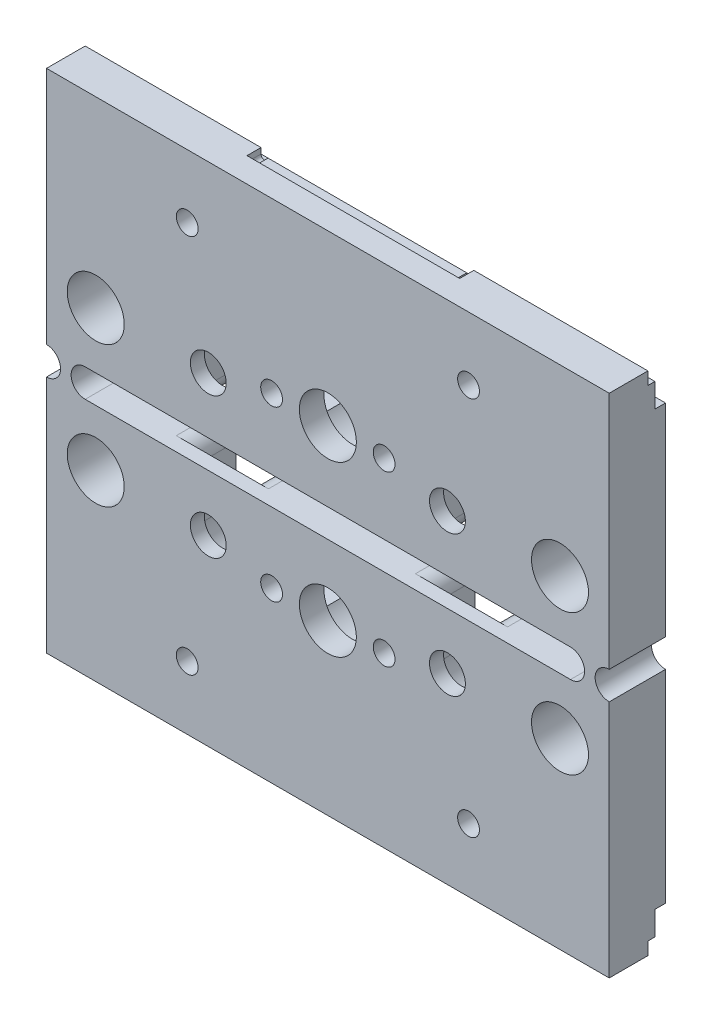
SolidWorks part; units mm, degrees
ref_plane "前视基准面" through (0, 0, 0) normal (0, 0, 1) x (1, 0, 0)
ref_plane "上视基准面" through (0, 0, 0) normal (0, 1, 0) x (1, 0, 0)
ref_plane "右视基准面" through (0, 0, 0) normal (1, 0, 0) x (0, 0, -1)
sketch "前视图草图" plane through (0, 0, 0) normal (0, 0, 1) x (1, 0, 0)
  line L0 (0, 0) -> (8.5179, 0) construction
  line L1 (0, 0) -> (0, 5.4227) construction
sketch "草图2" plane through (0, 0, 0) normal (0, 0, 1) x (1, 0, 0)
  line L0 (0, 0) -> (80, 0)
  line L1 (-200000, 0) -> (200008.5179, 0) construction
  line L2 (80, 0) -> (80, 34)
  line L3 (80, 34) -> (0, 34)
  line L4 (0, -200000) -> (0, 200005.4227) construction
  line L5 (0, 34) -> (0, 0)
  circle A0 centre (7, 8) radius 4.05
  circle A1 centre (40, 10) radius 4.05
  circle A2 centre (73, 8) radius 4.05
  dimension "D3" = 8
  dimension "D5" = 10
  dimension "D9" = 8.1
  dimension "D10" = 8.1
  dimension "D11" = 8.1
  dimension "D1" = 34
  dimension "D2" = 80
  dimension "D4" = 7
  dimension "D6" = 7
  dimension "D7" = 8
  dimension "D8" = 40
extrude "凸台-拉伸1" add sketch "草图2" along normal blind 8
sketch "草图3" plane through (0, 0, 8) normal (0, 0, 1) x (1, 0, 0)
  line L0 (16.088, 8) -> (31.4805, 8) construction
  line L1 (7, 8) -> (7, 16.8386) construction
  line L2 (73, 8) -> (73, 16.5917) construction
  line L4 (-200000, 0) -> (200008.5179, 0) construction
  circle A2 centre (23, 8) radius 2.55
  circle A3 centre (57, 8) radius 2.55
  dimension "D4" = 5.1
  dimension "D5" = 5.1
  dimension "D1" = 8
  dimension "D2" = 16
  dimension "D3" = 16
extrude "切除-拉伸1" cut sketch "草图3" against normal through all
sketch "草图4" plane through (80, 0, 0) normal (1, 0, 0) x (0, 0, -1)
  line L1 (0, -200000) -> (0, 200005.4227) construction
  line L2 (-1.5, 32.2) -> (-2.5, 32.2)
  line L3 (-2.5, 32.2) -> (-2.5, 34)
  line L4 (-8, 34) -> (0, 34) construction
  line L5 (-2.5, 34) -> (0, 34)
  line L6 (-1.5, 32.2) -> (-1.5, 28.8)
  line L7 (-1.5, 28.8) -> (0, 28.8)
  line L8 (0, 28.8) -> (0, 34)
  dimension "D1" = 3.4
  dimension "D2" = 2.5
  dimension "D3" = 1.5
  dimension "D4" = 1.8
extrude "切除-拉伸2" cut sketch "草图4" against normal through all
sketch "草图5" plane through (0, 0, 8) normal (0, 0, 1) x (1, 0, 0)
  line L0 (40, 10) -> (56.5376, 10) construction
  circle A0 centre (40, 10) radius 8 construction
  circle A1 centre (48, 10) radius 1.55
  circle A2 centre (32, 10) radius 1.55
  dimension "D1" = 3.1
  dimension "D2" = 3.1
  dimension "D3" = 16
extrude "切除-拉伸3" cut sketch "草图5" against normal through all
sketch "草图7" plane through (0, 0, 0) normal (0, 0, -1) x (-1, 0, 0)
  line L0 (-40, 12) -> (-40, -8.3696) construction
  line L1 (-23, 10) -> (-23, -2.3368) construction
  line L2 (200000, 0) -> (-200008.5179, 0) construction
  line L6 (-27.05, 10) -> (-27.05, 2.5)
  line L7 (-29.55, 0) -> (-16.45, 0)
  line L8 (-18.95, 2.5) -> (-18.95, 10)
  line L9 (-23, 8) -> (-23, 15.9045) construction
  line L13 (0, -200000) -> (0, 200005.4227) construction
  line L14 (-57, 8) -> (-57, 15.9045) construction
  line L15 (-57, 10) -> (-57, -2.3368) construction
  line L16 (-61.05, 2.5) -> (-61.05, 10)
  line L17 (-50.45, 0) -> (-63.55, 0)
  line L18 (-52.95, 10) -> (-52.95, 2.5)
  arc A1 (-18.95, 10) -> (-27.05, 10) centre (-23, 10) ccw
  arc A4 (-29.55, 0) -> (-27.05, 2.5) centre (-29.55, 2.5) ccw
  arc A5 (-18.95, 2.5) -> (-16.45, 0) centre (-16.45, 2.5) ccw
  arc A7 (-61.05, 2.5) -> (-63.55, 0) centre (-63.55, 2.5) cw
  arc A8 (-50.45, 0) -> (-52.95, 2.5) centre (-50.45, 2.5) cw
  arc A9 (-61.05, 10) -> (-52.95, 10) centre (-57, 10) cw
  dimension "D1" = 40
  dimension "D4" = 8.1
  dimension "D7" = 2.5
  dimension "D8" = 2.5
  dimension "D3" = 10
extrude "切除-拉伸4" cut sketch "草图7" against normal blind 6
sketch "草图8" plane through (0, 0, 0) normal (0, 0, -1) x (-1, 0, 0)
  line L0 (-40, 10) -> (-57.3165, 10) construction
  line L1 (-40, 20) -> (-40, 35.6562) construction
  line L2 (-30.5, 12.85) -> (-49.5, 12.85)
  line L3 (-49.5, 7.15) -> (-30.5, 7.15)
  line L4 (200000, 0) -> (-200008.5179, 0) construction
  arc A0 (-30.5, 7.15) -> (-30.5, 12.85) centre (-30.5, 10) ccw
  arc A1 (-49.5, 12.85) -> (-49.5, 7.15) centre (-49.5, 10) ccw
  dimension "D1" = 5.7
  dimension "D2" = 9.5
  dimension "D3" = 9.5
  dimension "D4" = 10
extrude "切除-拉伸5" cut sketch "草图8" against normal blind 4.5
sketch "草图20" plane through (0, 0, 0) normal (0, 0, -1) x (-1, 0, 0)
  circle A0 centre (-40, 10) radius 5.5
  dimension "D1" = 11
extrude "切除-拉伸12" cut sketch "草图20" against normal blind 4.5
sketch "草图25" plane through (0, 0, 0) normal (0, 0, -1) x (-1, 0, 0)
  line L0 (-51.4471, 25) -> (-40.1512, 25) construction
  line L1 (-60, 37.1428) -> (-60, 21.9179) construction
  line L2 (-20, 37.1428) -> (-20, 21.9179) construction
  line L3 (0, 34) -> (-80, 34) construction
  line L4 (-80, 0) -> (-80, 28.8) construction
  line L5 (0, -200000) -> (0, 200005.4227) construction
  circle A0 centre (-60, 25) radius 1.55
  circle A1 centre (-20, 25) radius 1.55
  dimension "D4" = 3.1
  dimension "D5" = 3.1
  dimension "D1" = 9
  dimension "D2" = 20
  dimension "D3" = 20
extrude "切除-拉伸13" cut sketch "草图25" against normal through all
sketch "草图19" plane through (0, 0, 2.5) normal (0, 0, -1) x (-1, 0, 0)
  line L0 (0, 34) -> (-80, 34) construction
  line L1 (-25, 34) -> (-55.2479, 34)
  line L2 (-25, 34) -> (-25, 33.2)
  line L3 (-26, 33.2) -> (-54.2479, 33.2)
  line L4 (-55.2479, 34) -> (-55.2479, 33.2)
  line L5 (0, -200000) -> (0, 200005.4227) construction
  line L7 (0, 32.2) -> (-80, 32.2) construction
  line L8 (-56.3335, 32.7) -> (-52.9089, 32.7) construction
  line L9 (-55.2479, 1028.5823) -> (-55.2479, 33.2) construction
  line L10 (-25, 1028.5823) -> (-25, 32.7) construction
  line L11 (-55.2479, 32.7) -> (-55.2479, -973.3) construction
  line L12 (-25, 32.7) -> (-25, -973.3) construction
  arc A3 (-55.2479, 33.2) -> (-54.2479, 33.2) centre (-54.7479, 33.2) ccw
  arc A6 (-26, 33.2) -> (-25, 33.2) centre (-25.5, 33.2) ccw
  dimension "D3" = 1
  dimension "D4" = 1
  dimension "D2" = 0.8
  dimension "D1" = 0.5
  dimension "D9" = 25
extrude "切除-拉伸11" cut sketch "草图19" against normal blind 2
sketch "草图22" plane through (0, 0, 8) normal (0, 0, 1) x (1, 0, 0)
  line L1 (0, -200000) -> (0, 200005.4227) construction
  line L2 (0, -4) -> (5.5, -4)
  line L4 (80, 0) -> (74.5, 0)
  line L5 (3.5, 1.9875) -> (3.5, -4.1402) construction
  line L6 (76.5, -11.5647) -> (76.5, -5.1636) construction
  line L7 (80, 0) -> (80, 34) construction
  line L8 (74.5, -4) -> (80, -4)
  line L9 (5.5, 0) -> (0, 0)
  line L10 (78, -2.9635) -> (78, -4.3032) construction
  line L11 (2, -8.393) -> (2, -15.1693) construction
  arc A0 (5.5, 0) -> (5.5, -4) centre (5.5, -2) ccw
  arc A1 (74.5, -4) -> (74.5, 0) centre (74.5, -2) ccw
  arc A2 (0, -4) -> (0, 0) centre (0, -2) ccw
  arc A3 (80, 0) -> (80, -4) centre (80, -2) ccw
  dimension "D1" = 3.5
  dimension "D2" = 3.5
  dimension "D3" = 4
  dimension "D4" = 2
  dimension "D5" = 2
extrude "凸台-拉伸2" add sketch "草图22" against normal blind 8
ref_plane "基准面1" through (0, -2, 0) normal (0, -1, 0) x (-1, 0, 0)
mirror "镜向2" about plane through (0, -2, 0) normal (0, -1, 0) of "切除-拉伸13", "切除-拉伸11", "切除-拉伸12", "切除-拉伸5", "切除-拉伸4", "切除-拉伸2", "切除-拉伸1", "凸台-拉伸1", "切除-拉伸3"
sketch "草图23" plane through (0, 0, 0) normal (0, 0, -1) x (-1, 0, 0)
  line L0 (-80, 0) -> (0, 0)
  line L1 (0, 0) -> (0, -4)
  line L2 (0, -4) -> (-80, -4)
  line L3 (-80, -4) -> (-80, 0)
sketch "草图24" plane through (0, 0, 8) normal (0, 0, 1) x (1, 0, 0)
  line L0 (80, -4) -> (80, 0)
  line L1 (80, 0) -> (0, 0)
  line L2 (0, 0) -> (0, -4)
  line L3 (0, -4) -> (80, -4)
